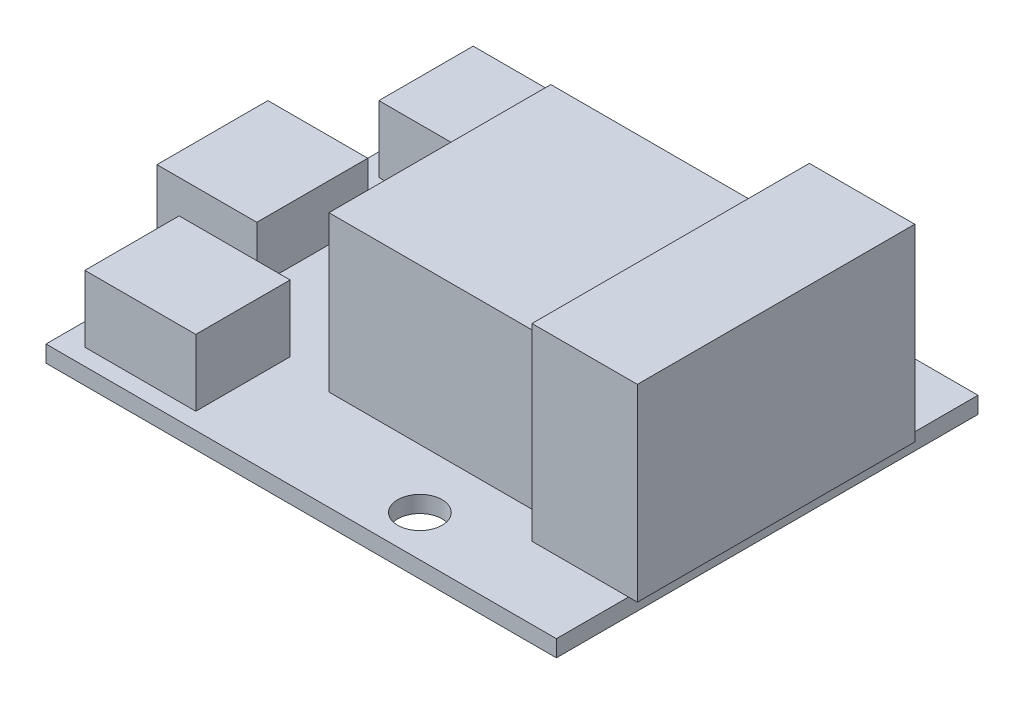
SolidWorks part; units mm, degrees
ref_plane "Plano frontal" through (0, 0, 0) normal (0, 0, 1) x (1, 0, 0)
ref_plane "Plano superior" through (0, 0, 0) normal (0, 1, 0) x (1, 0, 0)
ref_plane "Plano direito" through (0, 0, 0) normal (1, 0, 0) x (0, 0, -1)
sketch "Esboço1" plane through (0, 0, 0) normal (0, 1, 0) x (1, 0, 0)
  line L0 (7, -15.3) -> (7, 15.3) construction
  line L1 (-23, -19) -> (23, -19)
  line L2 (-23, -19) -> (-23, 19)
  line L3 (-23, 19) -> (23, 19)
  line L4 (23, -19) -> (23, 19)
  line L5 (-23, -19) -> (23, 19) construction
  line L6 (-23, 19) -> (23, -19) construction
  line L7 (7, -17.3) -> (7, -19) construction
  line L8 (9, -15.3) -> (23, -15.3) construction
  circle A0 centre (7, -15.3) radius 2
  circle A1 centre (7, 15.3) radius 2
  point P0 (0, 0)
  point P10 (7, 0)
  dimension "D3" = 4
  dimension "D1" = 46
  dimension "D2" = 38
  dimension "D4" = 1.7
  dimension "D5" = 30.6
  dimension "D6" = 14
extrude "Ressalto-extrusão1" add sketch "Esboço1" along normal blind 1.5
sketch "Esboço2" plane through (0, 1.5, 0) normal (0, 1, 0) x (1, 0, 0)
  line L0 (-23, 19) -> (-23, -19) construction
  line L1 (-27, 5) -> (-18, 5)
  line L2 (-27, 5) -> (-27, -5)
  line L3 (-27, -5) -> (-18, -5)
  line L4 (-18, 5) -> (-18, -5)
  line L5 (-21, -9) -> (-11, -9)
  line L6 (-21, -9) -> (-21, -17.5)
  line L7 (-21, -17.5) -> (-11, -17.5)
  line L8 (-11, -9) -> (-11, -17.5)
  line L9 (-21, 9) -> (-11, 9)
  line L10 (-21, 9) -> (-21, 17.5)
  line L11 (-21, 17.5) -> (-11, 17.5)
  line L12 (-11, 9) -> (-11, 17.5)
  line L17 (-6.5, 10) -> (13.5, 10)
  line L18 (-6.5, 10) -> (-6.5, -10)
  line L19 (-6.5, -10) -> (13.5, -10)
  line L20 (13.5, 10) -> (13.5, -10)
  line L21 (14.3, 12.5) -> (23.8, 12.5)
  line L22 (14.3, 12.5) -> (14.3, -12.5)
  line L23 (14.3, -12.5) -> (23.8, -12.5)
  line L24 (23.8, 12.5) -> (23.8, -12.5)
  line L25 (-16, -9) -> (-16, 9) construction
  line L26 (23, -19) -> (23, 19) construction
  point P14 (-6.5, 0)
  point P15 (23.8, 0)
  point P24 (-18, 0)
  point P30 (-16, 0)
  dimension "D1" = 9
  dimension "D2" = 4
  dimension "10" = 10
  dimension "D3" = 8.5
  dimension "D4" = 10
  dimension "D5" = 35
  dimension "D6" = 2
  dimension "D7" = 20
  dimension "D8" = 20
  dimension "D9" = 16.5
  dimension "D10" = 9.5
  dimension "D11" = 9.5
  dimension "D12" = 25
  dimension "D13" = 0.8
extrude "Ressalto-extrusão2" add sketch "Esboço2" along normal blind 5 contours L4 L1 L2 L3 | L2 L3 L4 L1 region at (-22.5, 1.5, 0)
extrude "Ressalto-extrusão3" add sketch "Esboço2<3>" along normal blind 6 contours L7 L8 L5 L6 | L9 L12 L11 L10
sketch "Esboço2<3>" plane through (0, 1.5, 0) normal (0, 1, 0) x (1, 0, 0) same geometry as "Esboço2"
extrude "Ressalto-extrusão4" add sketch "Esboço2<4>" along normal blind 14 contours L19 L20 L17 L18
sketch "Esboço2<4>" plane through (0, 1.5, 0) normal (0, 1, 0) x (1, 0, 0) same geometry as "Esboço2"
extrude "Ressalto-extrusão5" add sketch "Esboço2<5>" along normal blind 17 contours L23 L24 L21 L22
sketch "Esboço2<5>" plane through (0, 1.5, 0) normal (0, 1, 0) x (1, 0, 0) same geometry as "Esboço2"
